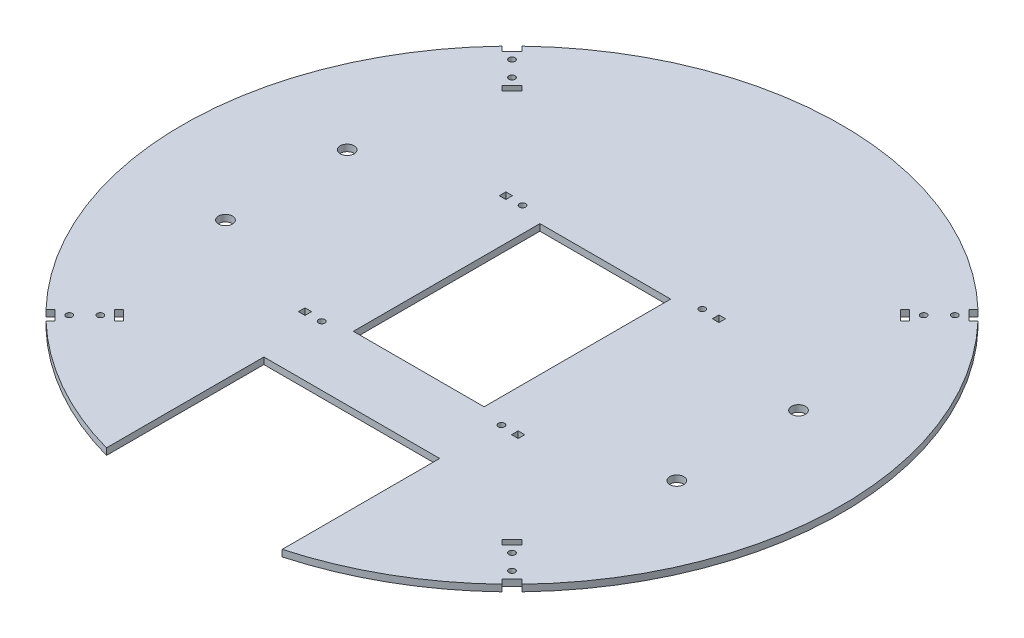
SolidWorks part; units mm, degrees
material "Acrylic (Medium-high impact)"
ref_plane "Front Plane" through (0, 0, 0) normal (0, 0, 1) x (1, 0, 0)
ref_plane "Top Plane" through (0, 0, 0) normal (0, 1, 0) x (1, 0, 0)
ref_plane "Right Plane" through (0, 0, 0) normal (1, 0, 0) x (0, 0, -1)
sketch "Sketch1" plane through (0, 0, 0) normal (0, 1, 0) x (1, 0, 0)
  line L0 (-29.75, -42.45) -> (-29.75, 42.45)
  line L1 (-31.75, -44.45) -> (31.75, -44.45) construction
  line L2 (-31.75, -44.45) -> (-31.75, 44.45) construction
  line L3 (-31.75, 44.45) -> (31.75, 44.45) construction
  line L4 (31.75, -44.45) -> (31.75, 44.45) construction
  line L5 (-31.75, -44.45) -> (31.75, 44.45) construction
  line L6 (-31.75, 44.45) -> (31.75, -44.45) construction
  line L7 (-29.75, 42.45) -> (29.75, 42.45)
  line L8 (29.75, -42.45) -> (29.75, 42.45)
  line L9 (-29.75, -42.45) -> (29.75, -42.45)
  circle A0 centre (0, 0) radius 150
  point P0 (0, 0)
  dimension "D3" = 300
  dimension "D1" = 63.5
  dimension "D2" = 88.9
  dimension "D4" = 2
extrude "Boss-Extrude1" add sketch "Sketch1" along normal blind 3
sketch "Sketch3" plane through (0, 3, 0) normal (0, 1, 0) x (1, 0, 0)
  line L0 (-42.4, 47.2) -> (-39.4, 44.2) construction
  line L1 (42.4, 47.2) -> (39.4, 44.2) construction
  line L2 (0, 0) -> (25.2091, 0) construction
  line L7 (-50, 44.2) -> (-47, 44.2)
  line L8 (-47, 44.2) -> (-47, 47.2)
  line L9 (-47, 47.2) -> (-50, 47.2)
  line L10 (-50, 47.2) -> (-50, 44.2)
  line L11 (-50, 44.2) -> (-47, 44.2)
  line L12 (-47, 44.2) -> (-47, 47.2)
  line L13 (-47, 47.2) -> (-50, 47.2)
  line L14 (-50, 47.2) -> (-50, 44.2)
  line L15 (47, 44.2) -> (50, 44.2)
  line L16 (50, 44.2) -> (50, 47.2)
  line L17 (50, 47.2) -> (47, 47.2)
  line L18 (47, 47.2) -> (47, 44.2)
  line L19 (47, 44.2) -> (50, 44.2)
  line L20 (50, 44.2) -> (50, 47.2)
  line L21 (50, 47.2) -> (47, 47.2)
  line L22 (47, 47.2) -> (47, 44.2)
  line L23 (47, -47.2) -> (50, -47.2) construction
  line L24 (50, -47.2) -> (50, -44.2) construction
  line L25 (50, -44.2) -> (47, -44.2) construction
  line L26 (47, -44.2) -> (47, -47.2) construction
  line L31 (-50, -47.2) -> (-47, -47.2) construction
  line L32 (-47, -47.2) -> (-47, -44.2) construction
  line L33 (-47, -44.2) -> (-50, -44.2) construction
  line L34 (-50, -44.2) -> (-50, -47.2) construction
  line L51 (47, -47.2) -> (50, -47.2)
  line L52 (50, -47.2) -> (50, -44.2)
  line L53 (50, -44.2) -> (47, -44.2)
  line L54 (47, -44.2) -> (47, -47.2)
  line L55 (-50, -47.2) -> (-47, -47.2)
  line L56 (-47, -47.2) -> (-47, -44.2)
  line L57 (-47, -44.2) -> (-50, -44.2)
  line L58 (-50, -44.2) -> (-50, -47.2)
  line L59 (0, 0) -> (0, -93.4335) construction
  circle A0 centre (-40.9, 45.7) radius 1.4224
  circle A1 centre (40.9, 45.7) radius 1.4224
  circle A2 centre (40.9, -45.7) radius 1.4224
  circle A3 centre (-40.9, -45.7) radius 1.4224
  circle A4 centre (-102.7, 27.7) radius 3.175
  circle A5 centre (-102.7, -27.7) radius 3.175
  circle A6 centre (102.7, 27.7) radius 3.175
  circle A7 centre (102.7, -27.7) radius 3.175
  dimension "D1" = 2.8448
  dimension "D4" = 6.35
  dimension "D2" = 0
  dimension "D3" = 0
extrude "Cut-Extrude1" cut sketch "Sketch3" against normal blind 10
sketch "Sketch4" plane through (0, 3, 0) normal (0, 1, 0) x (1, 0, 0)
  line L1 (-52.6396, -60.6627) -> (52.6396, -60.6627)
  line L2 (-52.6396, -60.6627) -> (-52.6396, 60.6627)
  line L3 (-52.6396, 60.6627) -> (52.6396, 60.6627)
  line L4 (52.6396, -60.6627) -> (52.6396, 60.6627)
  line L5 (-52.6396, -60.6627) -> (52.6396, 60.6627) construction
  line L6 (-52.6396, 60.6627) -> (52.6396, -60.6627) construction
  line L7 (-176.3133, 139.7199) -> (176.3133, 139.7199)
  line L8 (-176.3133, 139.7199) -> (-176.3133, -139.7199)
  line L9 (-176.3133, -139.7199) -> (176.3133, -139.7199)
  line L10 (176.3133, 139.7199) -> (176.3133, -139.7199)
  line L11 (-176.3133, 139.7199) -> (176.3133, -139.7199) construction
  line L12 (-176.3133, -139.7199) -> (176.3133, 139.7199) construction
  point P0 (0, 0)
  point P6 (0, 0)
extrude "Cut-Extrude2" [suppressed] cut sketch "Sketch4" against normal blind 10
sketch "Sketch6" plane through (0, 3, 0) normal (0, 1, 0) x (1, 0, 0)
  line L0 (-29.75, -42.45) -> (29.75, -42.45) construction
  line L1 (-40, -72.93) -> (40, -72.93)
  line L2 (-40, -72.93) -> (-40, -161.3295)
  line L3 (-40, -161.3295) -> (40, -161.3295)
  line L4 (40, -72.93) -> (40, -161.3295)
  line L5 (-40, -72.93) -> (40, -161.3295) construction
  line L6 (-40, -161.3295) -> (40, -72.93) construction
  point P0 (0, -117.1298)
  dimension "D1" = 30.48
  dimension "D2" = 80
extrude "Cut-Extrude3" cut sketch "Sketch6" against normal blind 3
sketch "Sketch7" plane through (0, 3, 0) normal (0, 1, 0) x (1, 0, 0)
  line L0 (0, 0) -> (0, 150) construction
  line L1 (0, 0) -> (-106.066, 106.066) construction
  line L2 (0, 0) -> (106.066, 106.066) construction
  line L3 (0, 0) -> (106.066, -106.066)
  line L4 (0, 0) -> (-106.066, -106.066) construction
  circle A0 centre (0, 0) radius 150 construction
  point P13 (0, 0)
  dimension "D1" = 45
  dimension "D2" = 4
ref_axis "Axis1" through (0, 3, 0) along (0, -1, 0)
ref_plane "Plane1" through (0, 0, 0) normal (0.7071, 0, 0.7071) x (0, -1, 0)
sketch "Sketch8" plane through (0, 0, 0) normal (0, -1, 0) x (1, 0, 0)
  line L0 (99.5234, 104.0136) -> (102.002, 97.5119) construction
  line L1 (92.4524, 96.9425) -> (94.9309, 90.4408) construction
  line L2 (103.821, 108.3111) -> (108.3111, 103.821) construction
  line L3 (106.1898, 101.6996) -> (108.3111, 103.821) construction
  line L4 (101.6996, 106.1898) -> (103.821, 108.3111) construction
  line L5 (101.6996, 106.1898) -> (106.1898, 101.6996) construction
  line L6 (90.6334, 86.1433) -> (92.7547, 88.2646)
  line L7 (92.7547, 88.2646) -> (88.2646, 92.7547)
  line L8 (88.2646, 92.7547) -> (86.1433, 90.6334)
  line L9 (86.1433, 90.6334) -> (90.6334, 86.1433)
  line L10 (90.6334, 86.1433) -> (92.7547, 88.2646)
  line L11 (92.7547, 88.2646) -> (88.2646, 92.7547)
  line L12 (88.2646, 92.7547) -> (86.1433, 90.6334)
  line L13 (86.1433, 90.6334) -> (90.6334, 86.1433)
  line L14 (103.821, 108.3111) -> (108.3111, 103.821)
  line L15 (106.1898, 101.6996) -> (108.3111, 103.821)
  line L16 (101.6996, 106.1898) -> (103.821, 108.3111)
  line L17 (101.6996, 106.1898) -> (106.1898, 101.6996)
  line L18 (86.1433, -90.6334) -> (88.2646, -92.7547)
  line L19 (88.2646, -92.7547) -> (92.7547, -88.2646)
  line L20 (92.7547, -88.2646) -> (90.6334, -86.1433)
  line L21 (90.6334, -86.1433) -> (86.1433, -90.6334)
  line L22 (108.3111, -103.821) -> (103.821, -108.3111)
  line L23 (101.6996, -106.1898) -> (103.821, -108.3111)
  line L24 (106.1898, -101.6996) -> (108.3111, -103.821)
  line L25 (106.1898, -101.6996) -> (101.6996, -106.1898)
  line L26 (104.0136, -99.5234) -> (97.5119, -102.002) construction
  line L27 (96.9425, -92.4524) -> (90.4408, -94.9309) construction
  line L28 (-90.6334, -86.1433) -> (-92.7547, -88.2646)
  line L29 (-92.7547, -88.2646) -> (-88.2646, -92.7547)
  line L30 (-88.2646, -92.7547) -> (-86.1433, -90.6334)
  line L31 (-86.1433, -90.6334) -> (-90.6334, -86.1433)
  line L32 (-103.821, -108.3111) -> (-108.3111, -103.821)
  line L33 (-106.1898, -101.6996) -> (-108.3111, -103.821)
  line L34 (-101.6996, -106.1898) -> (-103.821, -108.3111)
  line L35 (-101.6996, -106.1898) -> (-106.1898, -101.6996)
  line L36 (-99.5234, -104.0136) -> (-102.002, -97.5119) construction
  line L37 (-92.4524, -96.9425) -> (-94.9309, -90.4408) construction
  line L38 (-86.1433, 90.6334) -> (-88.2646, 92.7547)
  line L39 (-88.2646, 92.7547) -> (-92.7547, 88.2646)
  line L40 (-92.7547, 88.2646) -> (-90.6334, 86.1433)
  line L41 (-90.6334, 86.1433) -> (-86.1433, 90.6334)
  line L42 (-108.3111, 103.821) -> (-103.821, 108.3111)
  line L43 (-101.6996, 106.1898) -> (-103.821, 108.3111)
  line L44 (-106.1898, 101.6996) -> (-108.3111, 103.821)
  line L45 (-106.1898, 101.6996) -> (-101.6996, 106.1898)
  line L46 (-104.0136, 99.5234) -> (-97.5119, 102.002) construction
  line L47 (-96.9425, 92.4524) -> (-90.4408, 94.9309) construction
  circle A0 centre (100.7627, 100.7627) radius 1.4224
  circle A1 centre (93.6916, 93.6916) radius 1.4224
  circle A2 centre (100.7627, -100.7627) radius 1.4224
  circle A3 centre (93.6916, -93.6916) radius 1.4224
  circle A4 centre (-100.7627, -100.7627) radius 1.4224
  circle A5 centre (-93.6916, -93.6916) radius 1.4224
  circle A6 centre (-100.7627, 100.7627) radius 1.4224
  circle A7 centre (-93.6916, 93.6916) radius 1.4224
  point P71 (0, 0)
  dimension "D1" = 2.8448
  dimension "D2" = 0
  dimension "D3" = 4
ref_plane "Plane2" through (-90.6334, 0, 86.1433) normal (0, -1, 0) x (-1, 0, 0)
extrude "Cut-Extrude5" cut sketch "Sketch8" against normal blind 3
